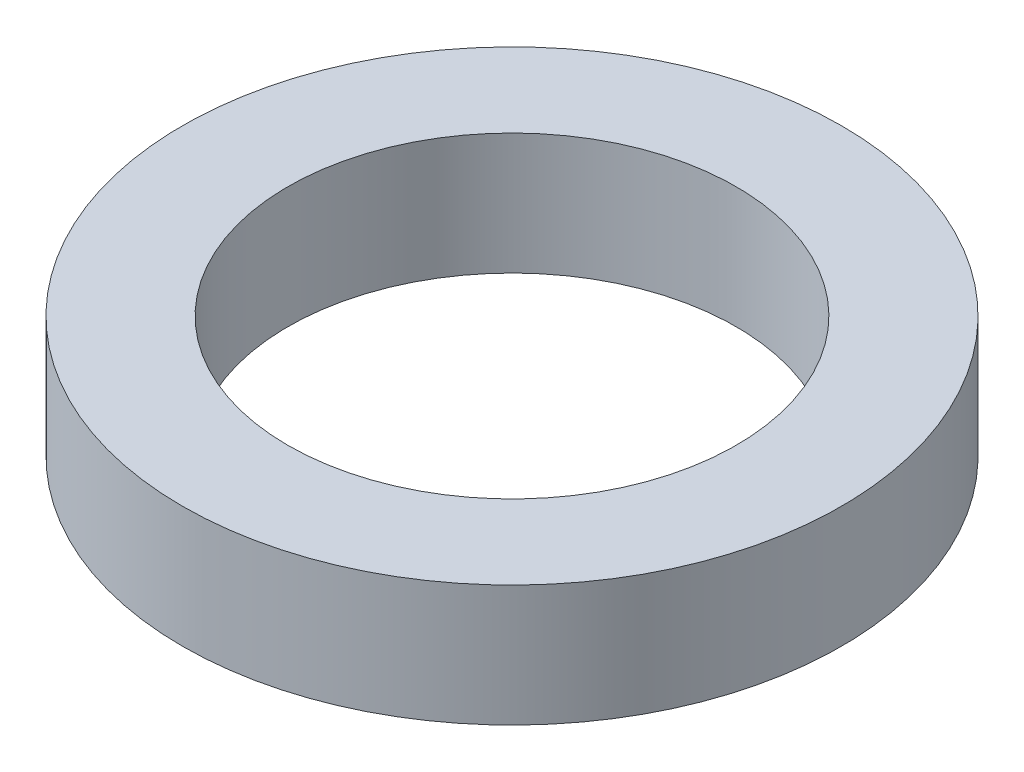
SolidWorks part; units mm, degrees
ref_plane "Front Plane" through (0, 0, 0) normal (0, 0, 1) x (1, 0, 0)
ref_plane "Top Plane" through (0, 0, 0) normal (0, 1, 0) x (1, 0, 0)
ref_plane "Right Plane" through (0, 0, 0) normal (1, 0, 0) x (0, 0, -1)
sketch "Sketch1" plane through (0, 0, 0) normal (0, 1, 0) x (1, 0, 0)
  circle A0 centre (0, 0) radius 62.5
  dimension "FLANGE_OD" = 125
extrude "Boss-Extrude1" add sketch "Sketch1" along normal blind 23
sketch "Sketch2" plane through (0, 0, 0) normal (0, 1, 0) x (1, 0, 0)
  circle A0 centre (0, 0) radius 42.5
  dimension "BORE_D" = 85
extrude "Cut-Extrude1" cut sketch "Sketch2" along normal through all
sketch "Sketch3" plane through (0, 23, 0) normal (0, 1, 0) x (1, 0, 0)
  circle A0 centre (0, 0) radius 25.3961 construction
  circle A1 centre (-25.3961, 0) radius 3.0744
  dimension "BOLT_D" = 6.1489
  dimension "BOLT_PCD" = 50.7922
extrude "Cut-Extrude2" cut sketch "Sketch3" against normal blind 20.944 rebuild error yes
pattern_circular "CirPattern1" count 5 over 360 rebuild error yes
